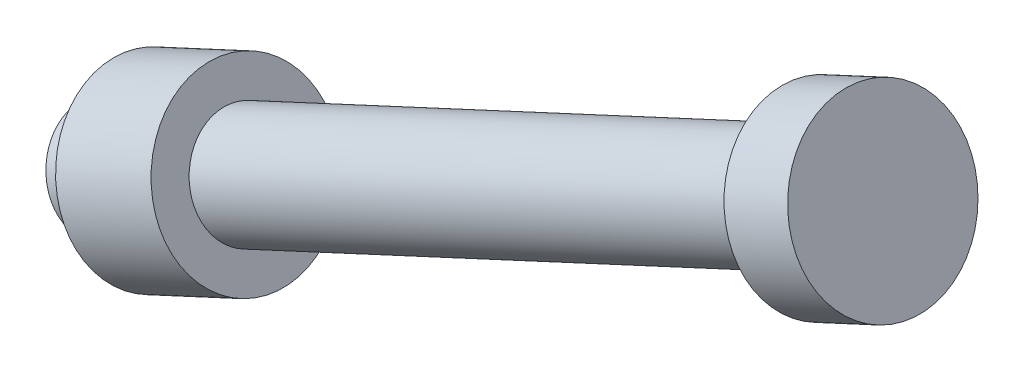
SolidWorks part; units mm, degrees
material "AISI 304"
ref_plane "Alzado" through (0, 0, 0) normal (0, 0, 1) x (1, 0, 0)
ref_plane "Planta" through (0, 0, 0) normal (0, 1, 0) x (1, 0, 0)
ref_plane "Vista lateral" through (0, 0, 0) normal (1, 0, 0) x (0, 0, -1)
sketch3d "Sk_Cabeza"
  line L0 (436.5934, 392.8864, 0) -> (440.2217, 394.5702, 0)
  dimension "D1" = 4
sweep "Cabeza" add path "Sk_Cabeza" circular profile diameter 10 parameters "D3"=10
sketch3d "Sk_Vastago"
  line L0 (395.775, 373.9428, 0) -> (436.5934, 392.8864, 0)
  dimension "D1" = 45
sweep "Vastago" add path "Sk_Vastago" circular profile diameter 6 parameters "D3"=6
cosmetic thread "Rosca cosmética1" parameters "D1"=45, "D2"=4.7731
sketch3d "Sk_Tuerca"
  line L0 (398.4962, 375.2057, 0) -> (403.9387, 377.7315, 0)
  dimension "D1" = 6
sweep "Tuerca" add path "Sk_Tuerca" circular profile diameter 10 parameters "D3"=10
sketch "Croquis23" plane through (468.4281, 217.3947, 0) normal (-0.9071, -0.421, 0) x (0, 0, 1)
  circle A0 centre (0, 172.5855) radius 3
  circle A1 centre (0, 172.5855) radius 3
curve "Hélice/Espiral1" pitch 0.5 height 3 turns 6
